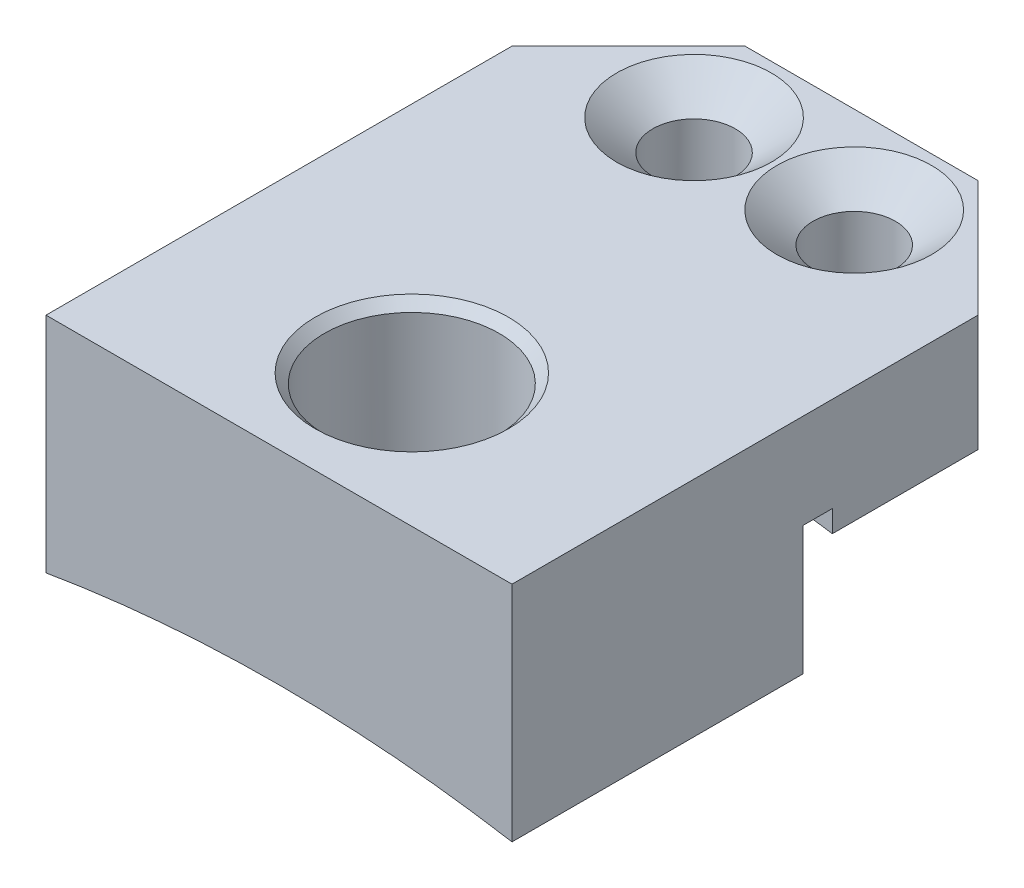
SolidWorks part; units mm, degrees
ref_plane "Front Plane" through (0, 0, 0) normal (0, 0, 1) x (1, 0, 0)
ref_plane "Top Plane" through (0, 0, 0) normal (0, 1, 0) x (1, 0, 0)
ref_plane "Right Plane" through (0, 0, 0) normal (1, 0, 0) x (0, 0, -1)
sketch "Sketch1" plane through (0, 0, 0) normal (0, 1, 0) x (1, 0, 0)
  line L0 (-12.7, 15.875) -> (12.7, -15.875) construction
  line L1 (-12.7, 15.875) -> (12.7, 15.875)
  line L2 (-12.7, 15.875) -> (-12.7, -15.875)
  line L3 (-12.7, -15.875) -> (12.7, -15.875)
  line L4 (12.7, 15.875) -> (12.7, -15.875)
  point P4 (0, 0)
  dimension "D1" = 25.4
  dimension "D2" = 31.75
extrude "Boss-Extrude1" add sketch "Sketch1" along normal blind 6.35
sketch "Sketch2" plane through (0, 0, 15.875) normal (0, 0, 1) x (1, 0, 0)
  line L0 (-12.7, 0) -> (12.7, 0)
  arc A0 (-12.7, 0) -> (12.7, 0) centre (0, -80.9502) cw
  dimension "D1" = 81.9404
extrude "Cut-Extrude1" cut sketch "Sketch2" against normal through all
sketch "Sketch3" plane through (0, 0, 15.875) normal (0, 0, 1) x (1, 0, 0)
  line L0 (-12.7, 6.35) -> (12.7, 6.35)
  line L1 (12.7, 6.35) -> (12.7, -5.816)
  line L2 (-12.7, 6.35) -> (-12.7, -5.816)
  arc A0 (-12.7, -5.816) -> (12.7, -5.816) centre (0, -80.9502) cw
  arc A1 (12.7, 0) -> (-12.7, 0) centre (0, -80.9502) ccw construction
  dimension "D1" = 76.2
extrude "Boss-Extrude2" add sketch "Sketch3" against normal blind 15.875
sketch "Sketch4" plane through (-12.7, 0, 0) normal (-1, 0, 0) x (0, 0, 1)
  line L1 (0, 0) -> (-1.5875, 0)
  line L2 (0, 0) -> (0, 1.1906)
  line L3 (0, 1.1906) -> (-1.5875, 1.1906)
  line L4 (-1.5875, 0) -> (-1.5875, 1.1906)
  dimension "D1" = 1.5875
  dimension "D2" = 1.1906
extrude "Cut-Extrude2" cut sketch "Sketch4" against normal through all
chamfer "Chamfer1" distance 6.35 angle 45 2 edges at (-12.7, 3.175, -15.875) (12.7, 3.175, -15.875)
sketch "Sketch5" plane through (0, 6.35, 0) normal (0, 1, 0) x (1, 0, 0)
  line L0 (-12.7, 9.525) -> (-12.7, -15.875) construction
  line L1 (-12.7, -15.875) -> (12.7, -15.875) construction
  circle A1 centre (0, -8.636) radius 1.524
  dimension "D1" = 3.048
  dimension "D2" = 12.7
  dimension "D3" = 7.239
extrude "Cut-Extrude3" cut sketch "Sketch5" against normal through all
hole_wizard "CSK for #8 Flat Head Machine Screw (100)1" positions "Sketch6" profile "Sketch7" countersink size "#8" standard "ANSI Inch" end condition through all
sketch "Sketch6" plane through (0, 6.35, 0) normal (0, 1, 0) x (1, 0, 0)
  line L0 (0, 15.875) -> (0, 4.8645) construction
  line L1 (6.35, 15.875) -> (-6.35, 15.875) construction
  point P0 (-4.3656, 11.1125)
  point P18 (4.3656, 11.1125)
  dimension "D1" = 4.7625
  dimension "D2" = 4.3656
sketch "Sketch7" plane through (-4.3656, 6.35, -11.1125) normal (1, 0, 0) x (0, 0, 1)
  line L0 (0, 0) -> (0, 12.166)
  line L1 (0, 12.166) -> (2.2479, 12.166)
  line L2 (2.2479, 12.166) -> (2.2479, 1.6518)
  line L3 (2.2479, 1.6518) -> (4.2164, 0)
  line L5 (4.2164, 0) -> (0, 0)
  line L6 (-2.2479, 1.6518) -> (-4.2164, 0) construction
  line L11 (0, -6.35) -> (0, 107.95) construction
  dimension "Thru Hole Dia." = 4.4958
  dimension "Thru Hole Depth" = 12.166
  dimension "Near C'Sink Dia." = 8.4328
  dimension "Near C'Sink Angle" = 100
sketch "Sketch8" plane through (0, 6.35, 0) normal (0, 1, 0) x (1, 0, 0)
  circle A0 centre (0, -8.636) radius 4.7625
  dimension "D1" = 9.525
extrude "Cut-Extrude4" cut sketch "Sketch8" against normal through all
chamfer "Chamfer2" distance 0.508 angle 45 1 edges at (0, 6.35, 13.3985)
